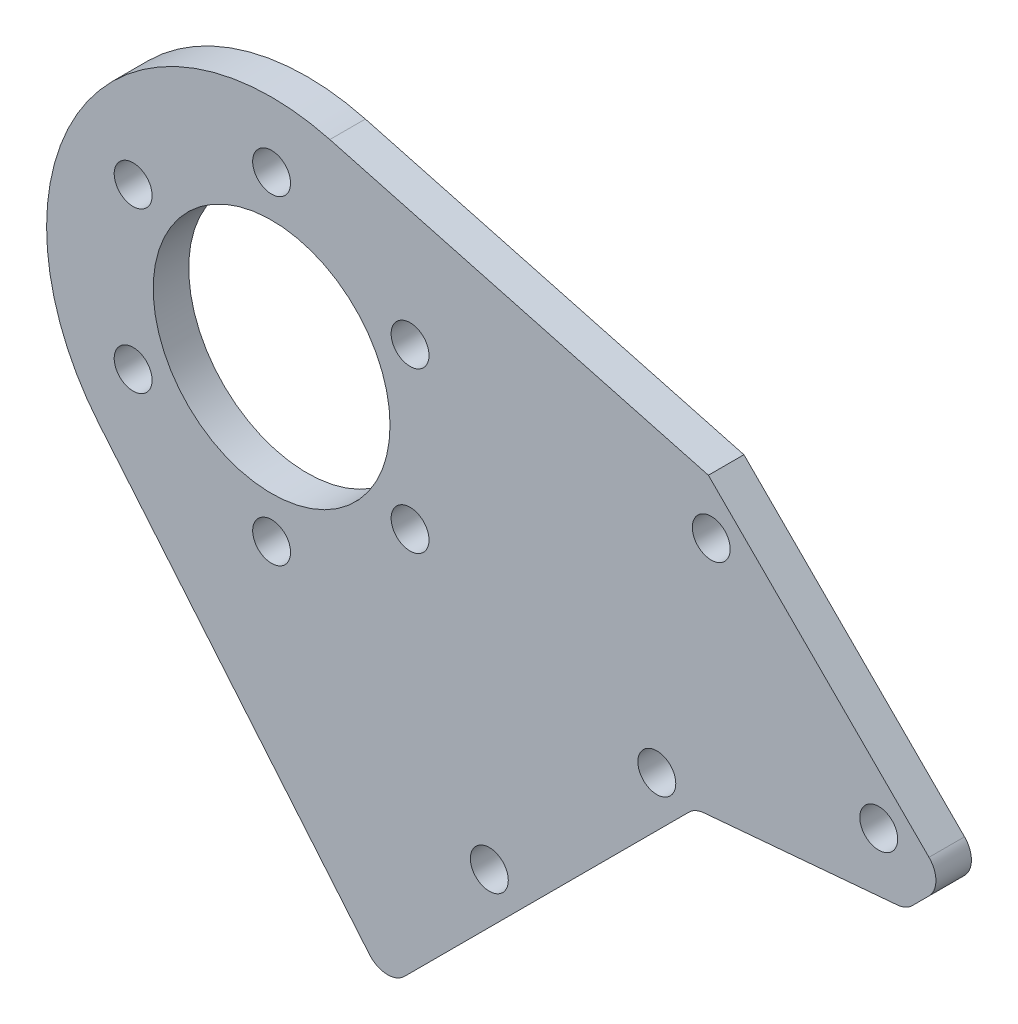
SolidWorks part; units mm, degrees
material "Thornel Mat VMA"
ref_plane "前视基准面" through (0, 0, 0) normal (0, 0, 1) x (1, 0, 0)
ref_plane "上视基准面" through (0, 0, 0) normal (0, 1, 0) x (1, 0, 0)
ref_plane "右视基准面" through (0, 0, 0) normal (1, 0, 0) x (0, 0, -1)
sketch "草图1" plane through (0, 0, 0) normal (0, 0, 1) x (1, 0, 0)
  circle A0 centre (0, 0) radius 13.5 construction
  circle A1 centre (0, 13.5) radius 1.6
  circle A2 centre (0, 0) radius 19
  circle A3 centre (0, 0) radius 10
  circle A4 centre (11.6913, 6.75) radius 1.6
  circle A5 centre (11.6913, -6.75) radius 1.6
  circle A6 centre (0, -13.5) radius 1.6
  circle A7 centre (-11.6913, -6.75) radius 1.6
  circle A8 centre (-11.6913, 6.75) radius 1.6
  point P16 (0, 0)
  dimension "D1" = 27
  dimension "D2" = 3.2
  dimension "D4" = 20
  dimension "D5" = 38
  dimension "D3" = 6
extrude "凸台-拉伸1" add sketch "草图1" along normal blind 3
sketch "草图2" plane through (0, 0, 3) normal (0, 0, 1) x (1, 0, 0)
  line L0 (24.7487, 21.9203) -> (55.5079, -8.8388)
  line L1 (23.3345, 23.3345) -> (0, 0) construction
  line L3 (0, 0) -> (69.4053, 0) construction
  line L5 (8.2623, -39.5663) -> (-14.5902, -12.1707)
  line L6 (37.1231, 5.3033) -> (51.2652, -8.8388) construction
  line L7 (11.2123, -39.6994) -> (35.2415, -15.6702)
  line L8 (36.4814, -15.0921) -> (52.8538, -13.6597)
  line L9 (55.5079, -11.6673) -> (54.0937, -13.0815)
  line L10 (21.9203, 21.9203) -> (13.435, 13.435)
  line L11 (32.5269, -14.1421) -> (18.3848, -28.2843) construction
  circle A0 centre (0, 0) radius 19 construction
  circle A3 centre (51.2652, -8.8388) radius 1.6
  circle A5 centre (37.1231, 5.3033) radius 1.6
  arc A6 (11.2123, -39.6994) -> (8.2623, -39.5663) centre (9.7981, -38.2852) cw
  arc A7 (35.2415, -15.6702) -> (36.4814, -15.0921) centre (36.6557, -17.0844) cw
  arc A8 (55.5079, -8.8388) -> (55.5079, -11.6673) centre (54.0937, -10.253) cw
  arc A10 (54.0937, -13.0815) -> (52.8538, -13.6597) centre (52.6795, -11.6673) cw
  arc A11 (-14.5902, -12.1707) -> (13.435, 13.435) centre (0, 0) ccw
  circle A13 centre (18.3848, -28.2843) radius 1.6
  circle A14 centre (32.5269, -14.1421) radius 1.6
  arc A15 (24.7487, 21.9203) -> (21.9203, 21.9203) centre (23.3345, 20.5061) ccw
  point P23 (-8.1023, -20.1604)
  point P26 (0, 0)
  point P31 (0, 0)
  point P32 (0, 0)
  point P35 (12.3744, 12.3744)
  dimension "D2" = 3.2
  dimension "D3" = 2
  dimension "D4" = 2
  dimension "D8" = 20
  dimension "D10" = 5
  dimension "D11" = 2
  dimension "D18" = 2
  dimension "D1" = 45
  dimension "D5" = 36
  dimension "D6" = 20
  dimension "D7" = 42.5
  dimension "D9" = 3
  dimension "D12" = 33
  dimension "D13" = 2
  dimension "D14" = 140
  dimension "D15" = 15
  dimension "D16" = 20
  dimension "D17" = 3
extrude "凸台-拉伸2" add sketch "草图2" against normal up to surface (3 mm away) up to face at (19, 0, 0)
sketch "草图5" plane through (0, 0, 3) normal (0, 0, 1) x (1, 0, 0)
  line L0 (4.9176, 18.3526) -> (36.881, 9.788)
  line L1 (55.5079, -8.8388) -> (24.7487, 21.9203) construction
  line L2 (21.9203, 21.9203) -> (13.435, 13.435) construction
  line L3 (21.9203, 21.9203) -> (15.5134, 15.5134)
  line L4 (36.881, 9.788) -> (24.7487, 21.9203)
  line L5 (15.5134, 15.5134) -> (13.435, 13.435)
  arc A0 (13.435, 13.435) -> (-14.5902, -12.1707) centre (0, 0) ccw construction
  arc A1 (24.7487, 21.9203) -> (21.9203, 21.9203) centre (23.3345, 20.5061) ccw construction
  arc A2 (24.7487, 21.9203) -> (21.9203, 21.9203) centre (23.3345, 20.5061) ccw
  arc A3 (13.435, 13.435) -> (4.9176, 18.3526) centre (0, 0) ccw
  arc M5 (13.435, 13.435) -> (-14.5902, -12.1707) centre (0, 0) ccw
  line M14 (55.5079, -8.8388) -> (24.7487, 21.9203)
  arc M15 (24.7487, 21.9203) -> (21.9203, 21.9203) centre (23.3345, 20.5061) ccw
  line M16 (21.9203, 21.9203) -> (13.435, 13.435)
  dimension "D1" = 150
extrude "切除-拉伸1" cut sketch "草图5" against normal blind 10 contours L0 M16 M14 M15 region at (25.2586, 16.159, 3)
extrude "凸台-拉伸4" add sketch "草图5<4>" against normal up to surface (3 mm away) contours L0 M5 M16 region at (12.1592, 15.6127, 3) up to face at (29.0598, -9.8304, 0)
sketch "草图5<4>" plane through (0, 0, 3) normal (0, 0, 1) x (1, 0, 0) same geometry as "草图5"
